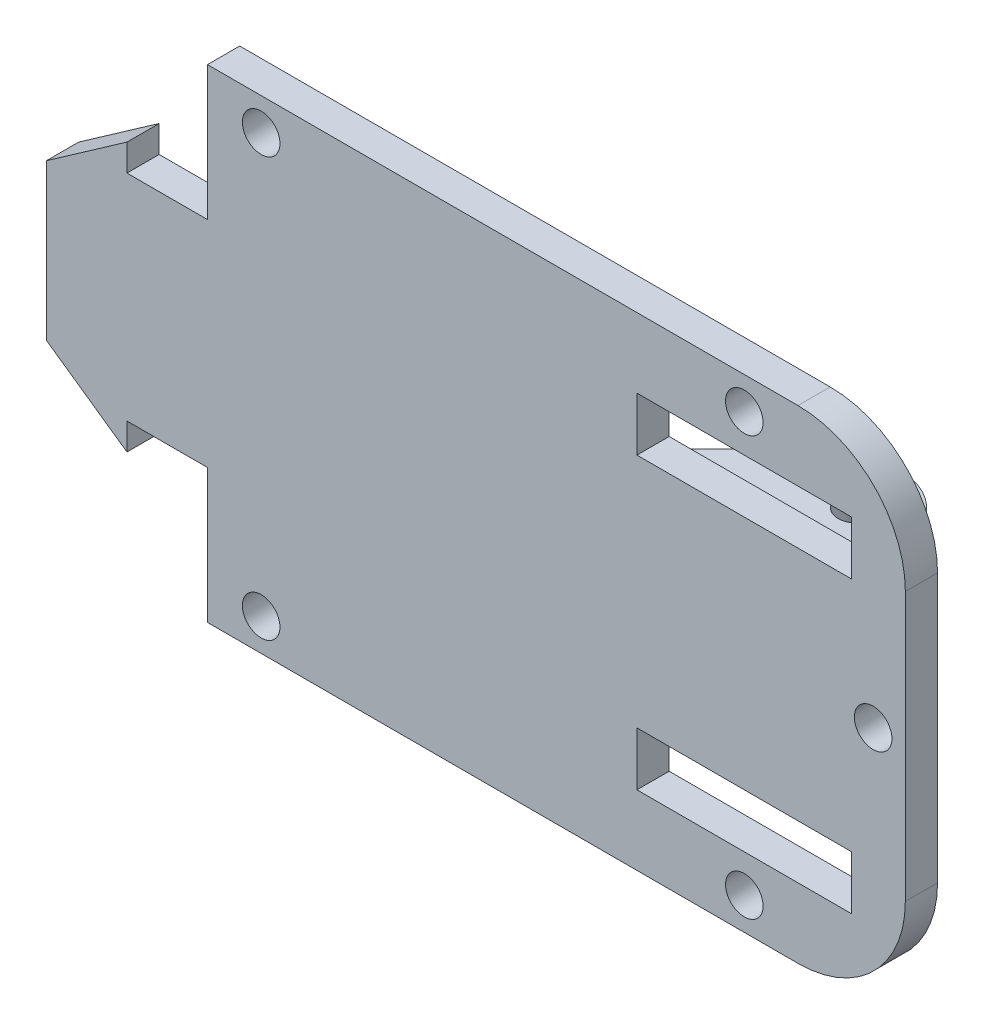
SolidWorks part; units mm, degrees
ref_plane "Front Plane" through (0, 0, 0) normal (0, 0, 1) x (1, 0, 0)
ref_plane "Top Plane" through (0, 0, 0) normal (0, 1, 0) x (1, 0, 0)
ref_plane "Right Plane" through (0, 0, 0) normal (1, 0, 0) x (0, 0, -1)
sketch "Sketch1" plane through (0, 0, 0) normal (0, 0, 1) x (1, 0, 0)
  line L1 (-44.437, 19.3432) -> (20.563, 19.3432)
  line L2 (-44.437, 19.3432) -> (-44.437, -25.6568)
  line L3 (-44.437, -25.6568) -> (20.563, -25.6568)
  line L4 (20.563, 19.3432) -> (20.563, -25.6568)
  dimension "D1" = 65
  dimension "D2" = 45
extrude "Boss-Extrude1" add sketch "Sketch1" along normal blind 3
sketch "Sketch2" plane through (0, 0, 0) normal (0, 0, -1) x (-1, 0, 0)
  line L5 (-0.563, -9.6568) -> (-10.563, -9.6568)
  line L6 (-0.563, -9.6568) -> (-0.563, 3.3432)
  line L7 (-0.563, 3.3432) -> (-10.563, 3.3432)
  line L8 (-10.563, -9.6568) -> (-10.563, 3.3432)
  line L10 (-20.563, -3.1568) -> (70.0438, -3.1568) construction
  line L11 (-20.563, -25.6568) -> (-20.563, 19.3432) construction
  dimension "D1" = 13
  dimension "D2" = 10
  dimension "D3" = 6.5
  dimension "D4" = 10
extrude "Boss-Extrude2" add sketch "Sketch2" along normal blind 12.5
sketch "Sketch3" plane through (0, 3.3432, 0) normal (0, 1, 0) x (1, 0, 0)
  line L0 (0.563, 2.5) -> (10.563, 2.5) construction
  line L2 (0.563, 12.5) -> (0.563, 0) construction
  line L3 (10.563, 12.5) -> (10.563, 0) construction
  line L4 (0.563, 2.5) -> (10.563, 12.5) construction
  line L5 (0.563, 12.5) -> (10.563, 2.5) construction
  line L6 (0.563, 0) -> (10.563, 0) construction
  circle A0 centre (5.563, 7.5) radius 1.75
  dimension "D1" = 2.5
extrude "Cut-Extrude1" cut sketch "Sketch3" against normal blind 13.5
sketch "Sketch4" plane through (0, 0, 0) normal (0, 0, -1) x (-1, 0, 0)
  line L0 (-0.563, -9.6568) -> (-0.563, 3.3432) construction
  line L1 (4.437, 7.8432) -> (-15.563, 7.8432)
  line L2 (4.437, 7.8432) -> (4.437, 12.8432)
  line L3 (4.437, 12.8432) -> (-15.563, 12.8432)
  line L4 (-15.563, 7.8432) -> (-15.563, 12.8432)
  line L6 (-0.563, 3.3432) -> (-10.563, 3.3432) construction
  dimension "D1" = 20
  dimension "D2" = 5
  dimension "D3" = 5
  dimension "D4" = 4.5
fillet "Fillet1" radius 6 1 edges at (10.563, -3.1568, -12.5)
chamfer "Chamfer1" distance 12 angle 45 1 edges at (0.563, -3.1568, 0)
fillet "Fillet3" radius 1 1 edges at (0.563, -3.1568, -12.5)
ref_plane "Plane1" through (0, -3.1568, 0) normal (0, 1, 0) x (1, 0, 0)
ref_axis "Axis1" through (5.563, -9.6568, -7.5) along (0, 1, 0)
ref_plane "Plane3" through (5.563, 0, 0) normal (1, 0, 0) x (0, 0, -1)
sketch "Sketch6" plane through (5.563, 0, 0) normal (1, 0, 0) x (0, 0, -1)
  line L0 (12.5, 3.3432) -> (6.5, 3.3432) construction
  line L1 (7.5, 12.8432) -> (18, 12.8432)
  line L2 (7.5, 12.8432) -> (7.5, 7.8432)
  line L3 (7.5, 7.8432) -> (18, 7.8432)
  line L4 (18, 12.8432) -> (18, 7.8432)
  line L5 (7.5, -9.6568) -> (7.5, 3.3432) construction
  dimension "D1" = 4.5
  dimension "D2" = 5
  dimension "D3" = 10.5
  dimension "D4" = 0
extrude "Cut-Extrude3" cut sketch "Sketch4" against normal blind 5
mirror "Mirror2" about plane through (0, -3.1568, 0) normal (0, 1, 0) of "Cut-Extrude3"
fillet "Fillet4" radius 10 2 edges at (20.563, -25.6568, 1.5) (20.563, 19.3432, 1.5)
chamfer "Chamfer2" distance 2.5 angle 45 1 edges at (10.563, -3.1568, 0)
sketch "Sketch7" plane through (0, 0, 0) normal (0, 0, -1) x (-1, 0, 0)
  line L0 (-5.563, -3.1568) -> (48.7662, -3.1568) construction
  line L1 (6.875, -3.1568) -> (-6.875, -3.1568) construction
  line L2 (-5.563, 2.2) -> (-5.563, -2.2) construction
  line L3 (-5.563, -3.1568) -> (-29.9947, -3.1568) construction
  line L4 (-5.563, -3.1568) -> (-5.563, 24.1217) construction
  line L5 (-5.563, -3.1568) -> (-5.563, -32.3324) construction
  line L6 (-5.563, -9.6568) -> (-5.563, 3.3432) construction
  line L7 (39.437, 24.1217) -> (39.437, -29.7158) construction
  line L8 (44.437, 19.3432) -> (44.437, -25.6568) construction
  line L9 (48.7662, 16.3432) -> (-29.9947, 16.3432) construction
  line L10 (-29.9947, -22.6568) -> (53.7379, -22.6568) construction
  line L11 (44.437, -25.6568) -> (-10.563, -25.6568) construction
  line L12 (-10.563, 19.3432) -> (44.437, 19.3432) construction
  line L13 (-17.563, 22.6825) -> (-17.563, -28.4074) construction
  line L14 (-20.563, -15.6568) -> (-20.563, 9.3432) construction
  circle A0 centre (-17.563, -3.1568) radius 1.75
  circle A2 centre (-5.563, 16.3432) radius 1.75
  circle A3 centre (39.437, 16.3432) radius 1.75
  circle A5 centre (39.437, -22.6568) radius 1.75
  circle A6 centre (-5.563, -22.6568) radius 1.75
  dimension "D1" = 5
  dimension "D5" = 3.5
  dimension "D6" = 3.5
  dimension "D2" = 3
  dimension "D3" = 3
  dimension "D4" = 3
extrude "Cut-Extrude4" cut sketch "Sketch7" against normal blind 5
sketch "Sketch8" plane through (0, 0, 0) normal (0, 0, -1) x (-1, 0, 0)
  line L0 (44.437, 19.3432) -> (44.437, -25.6568) construction
  line L1 (44.437, 9.3432) -> (59.437, 9.3432) construction
  line L2 (44.437, 9.3432) -> (44.437, -15.6568) construction
  line L3 (44.437, -15.6568) -> (59.437, -15.6568) construction
  line L4 (59.437, 9.3432) -> (59.437, -15.6568) construction
  line L5 (-10.563, 19.3432) -> (44.437, 19.3432) construction
  line L6 (44.437, -25.6568) -> (-10.563, -25.6568) construction
  line L7 (51.937, 9.3432) -> (51.937, -15.6568) construction
  line L8 (44.437, 6.8432) -> (51.937, 6.8432)
  line L9 (44.437, -13.1568) -> (51.937, -13.1568)
  line L10 (51.937, -15.6568) -> (59.437, -10.4053)
  line L11 (51.937, 9.3432) -> (59.437, 4.0916)
  line L12 (44.437, 6.8432) -> (44.437, -13.1568)
  line L13 (51.937, 9.3432) -> (51.937, 6.8432)
  line L14 (51.937, -13.1568) -> (51.937, -15.6568)
  line L15 (59.437, 4.0916) -> (59.437, -10.4053)
  dimension "D1" = 10
  dimension "D2" = 10
  dimension "D3" = 15
  dimension "D4" = 2.5
  dimension "D5" = 2.5
  dimension "D6" = 55
  dimension "D7" = 55
extrude "Boss-Extrude4" add sketch "Sketch8" against normal blind 3 contours L11 L15 L10 L14 L9 L12 L8 L13
